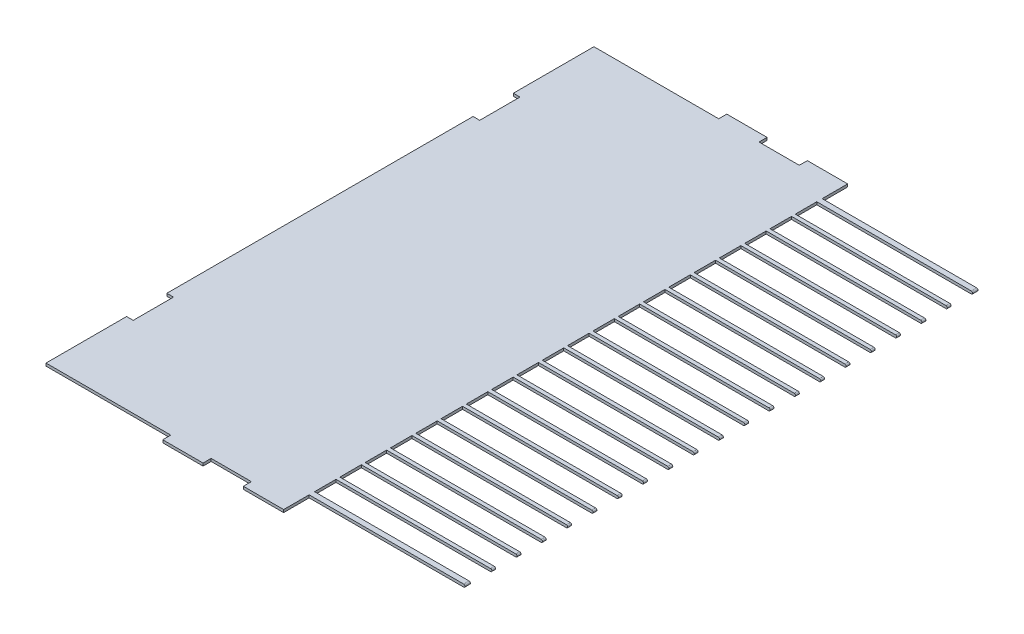
SolidWorks part; units mm, degrees
ref_plane "前视基准面" through (0, 0, 0) normal (0, 0, 1) x (1, 0, 0)
ref_plane "上视基准面" through (0, 0, 0) normal (0, 1, 0) x (1, 0, 0)
ref_plane "右视基准面" through (0, 0, 0) normal (1, 0, 0) x (0, 0, -1)
sketch "草图1" plane through (0, 0, 0) normal (0, 0, 1) x (1, 0, 0)
  line L0 (0, -1.0782) -> (0, -59.0782)
  line L1 (0, -59.0782) -> (150, -59.0782)
  line L3 (24.7207, -21.434) -> (24.7207, -1.0782)
  line L4 (24.7207, -1.0782) -> (0, -1.0782)
  line L5 (150, -59.0782) -> (150, -56.0782)
  line L6 (150, -56.0782) -> (24.7207, -21.434)
  dimension "D1" = 150
  dimension "D2" = 58
  dimension "D3" = 3
extrude "凸台-拉伸1" add sketch "草图1" along normal blind 0.5
sketch "草图2" plane through (0, 0, 0) normal (0, 0, -1) x (-1, 0, 0)
  line L1 (-24.7207, -1.0782) -> (0, -1.0782) construction
  line L2 (-2.47, -1.0782) -> (-2.47, -58.0782)
  line L4 (-149, -59.0782) -> (0, -59.0782)
  line L5 (0, -59.0782) -> (0, -1.0782)
  line L7 (-149, -58.0782) -> (-2.47, -58.0782)
  line L9 (-2.47, -1.0782) -> (0, -1.0782)
  arc A2 (-149, -58.0782) -> (-149, -59.0782) centre (-149, -58.5782) ccw
  point P14 (-150, -58.0782)
  point P17 (-150, -59.0782)
  dimension "D3" = 0.5
  dimension "D1" = 1
  dimension "D2" = 1
  dimension "D4" = 2.47
extrude "凸台-拉伸2" add sketch "草图2" along normal blind 104.5
mirror "镜向3" about plane through (149, -58.5782, -104.5) normal (0, 0, -1) of bodies 102 106
sketch "草图8" plane through (0, -58.0782, 0) normal (0, 1, 0) x (1, 0, 0)
  line L1 (151.4737, 1) -> (91.4737, 1)
  line L2 (151.4737, 1) -> (151.4737, 9)
  line L3 (151.4737, 9) -> (91.4737, 9)
  line L4 (91.4737, 1) -> (91.4737, 9)
  line L5 (151.4737, 1) -> (91.4737, 9) construction
  line L6 (151.4737, 9) -> (91.4737, 1) construction
  line L7 (2.47, 0) -> (149, 0) construction
  line L8 (91.4737, 11) -> (151.4737, 11)
  line L9 (91.4737, 11) -> (91.4737, 19)
  line L10 (91.4737, 19) -> (151.4737, 19)
  line L11 (151.4737, 11) -> (151.4737, 19)
  line L12 (91.4737, 11) -> (151.4737, 19) construction
  line L13 (91.4737, 19) -> (151.4737, 11) construction
  line L14 (91.4737, 20.4211) -> (91.4737, 28.4211)
  line L15 (91.4737, 20.4211) -> (151.4737, 20.4211)
  line L16 (151.4737, 20.4211) -> (151.4737, 28.4211)
  line L17 (91.4737, 28.4211) -> (151.4737, 28.4211)
  line L18 (91.4737, 29.8421) -> (91.4737, 37.8421)
  line L19 (91.4737, 29.8421) -> (151.4737, 29.8421)
  line L20 (151.4737, 29.8421) -> (151.4737, 37.8421)
  line L21 (91.4737, 37.8421) -> (151.4737, 37.8421)
  line L22 (91.4737, 39.2632) -> (91.4737, 47.2632)
  line L23 (91.4737, 39.2632) -> (151.4737, 39.2632)
  line L24 (151.4737, 39.2632) -> (151.4737, 47.2632)
  line L25 (91.4737, 47.2632) -> (151.4737, 47.2632)
  line L26 (91.4737, 48.6842) -> (91.4737, 56.6842)
  line L27 (91.4737, 48.6842) -> (151.4737, 48.6842)
  line L28 (151.4737, 48.6842) -> (151.4737, 56.6842)
  line L29 (91.4737, 56.6842) -> (151.4737, 56.6842)
  line L30 (91.4737, 58.1053) -> (91.4737, 66.1053)
  line L31 (91.4737, 58.1053) -> (151.4737, 58.1053)
  line L32 (151.4737, 58.1053) -> (151.4737, 66.1053)
  line L33 (91.4737, 66.1053) -> (151.4737, 66.1053)
  line L34 (91.4737, 67.5263) -> (91.4737, 75.5263)
  line L35 (91.4737, 67.5263) -> (151.4737, 67.5263)
  line L36 (151.4737, 67.5263) -> (151.4737, 75.5263)
  line L37 (91.4737, 75.5263) -> (151.4737, 75.5263)
  line L38 (91.4737, 76.9474) -> (91.4737, 84.9474)
  line L39 (91.4737, 76.9474) -> (151.4737, 76.9474)
  line L40 (151.4737, 76.9474) -> (151.4737, 84.9474)
  line L41 (91.4737, 84.9474) -> (151.4737, 84.9474)
  line L42 (91.4737, 86.3684) -> (91.4737, 94.3684)
  line L43 (91.4737, 86.3684) -> (151.4737, 86.3684)
  line L44 (151.4737, 86.3684) -> (151.4737, 94.3684)
  line L45 (91.4737, 94.3684) -> (151.4737, 94.3684)
  line L46 (91.4737, 95.7895) -> (91.4737, 103.7895)
  line L47 (91.4737, 95.7895) -> (151.4737, 95.7895)
  line L48 (151.4737, 95.7895) -> (151.4737, 103.7895)
  line L49 (91.4737, 103.7895) -> (151.4737, 103.7895)
  line L50 (91.4737, 105.2105) -> (91.4737, 113.2105)
  line L51 (91.4737, 105.2105) -> (151.4737, 105.2105)
  line L52 (151.4737, 105.2105) -> (151.4737, 113.2105)
  line L53 (91.4737, 113.2105) -> (151.4737, 113.2105)
  line L54 (91.4737, 114.6316) -> (91.4737, 122.6316)
  line L55 (91.4737, 114.6316) -> (151.4737, 114.6316)
  line L56 (151.4737, 114.6316) -> (151.4737, 122.6316)
  line L57 (91.4737, 122.6316) -> (151.4737, 122.6316)
  line L58 (91.4737, 124.0526) -> (91.4737, 132.0526)
  line L59 (91.4737, 124.0526) -> (151.4737, 124.0526)
  line L60 (151.4737, 124.0526) -> (151.4737, 132.0526)
  line L61 (91.4737, 132.0526) -> (151.4737, 132.0526)
  line L62 (91.4737, 133.4737) -> (91.4737, 141.4737)
  line L63 (91.4737, 133.4737) -> (151.4737, 133.4737)
  line L64 (151.4737, 133.4737) -> (151.4737, 141.4737)
  line L65 (91.4737, 141.4737) -> (151.4737, 141.4737)
  line L66 (91.4737, 142.8947) -> (91.4737, 150.8947)
  line L67 (91.4737, 142.8947) -> (151.4737, 142.8947)
  line L68 (151.4737, 142.8947) -> (151.4737, 150.8947)
  line L69 (91.4737, 150.8947) -> (151.4737, 150.8947)
  line L70 (91.4737, 152.3158) -> (91.4737, 160.3158)
  line L71 (91.4737, 152.3158) -> (151.4737, 152.3158)
  line L72 (151.4737, 152.3158) -> (151.4737, 160.3158)
  line L73 (91.4737, 160.3158) -> (151.4737, 160.3158)
  line L74 (91.4737, 161.7368) -> (91.4737, 169.7368)
  line L75 (91.4737, 161.7368) -> (151.4737, 161.7368)
  line L76 (151.4737, 161.7368) -> (151.4737, 169.7368)
  line L77 (91.4737, 169.7368) -> (151.4737, 169.7368)
  line L78 (91.4737, 171.1579) -> (91.4737, 179.1579)
  line L79 (91.4737, 171.1579) -> (151.4737, 171.1579)
  line L80 (151.4737, 171.1579) -> (151.4737, 179.1579)
  line L81 (91.4737, 179.1579) -> (151.4737, 179.1579)
  line L82 (91.4737, 180.5789) -> (91.4737, 188.5789)
  line L83 (91.4737, 180.5789) -> (151.4737, 180.5789)
  line L84 (151.4737, 180.5789) -> (151.4737, 188.5789)
  line L85 (91.4737, 188.5789) -> (151.4737, 188.5789)
  line L86 (91.4737, 190) -> (91.4737, 198)
  line L87 (91.4737, 190) -> (151.4737, 190)
  line L88 (151.4737, 190) -> (151.4737, 198)
  line L89 (91.4737, 198) -> (151.4737, 198)
  line L90 (2.47, 209) -> (149, 209) construction
  line L91 (151.4737, 200) -> (91.4737, 200)
  line L92 (151.4737, 200) -> (151.4737, 208)
  line L93 (151.4737, 208) -> (91.4737, 208)
  line L94 (91.4737, 200) -> (91.4737, 208)
  line L95 (151.4737, 200) -> (91.4737, 208) construction
  line L96 (151.4737, 208) -> (91.4737, 200) construction
  point P4 (121.4737, 5)
  point P11 (121.4737, 15)
  point P94 (121.4737, 204)
  dimension "D1" = 60
  dimension "D2" = 8
  dimension "D3" = 8
  dimension "D4" = 2
  dimension "D5" = 1
  dimension "D7" = 8
  dimension "D8" = 2
  dimension "D9" = 60
  dimension "D10" = 1
  dimension "D6" = 20
extrude "切除-拉伸2" cut sketch "草图8" against normal blind 10
extrude "凸台-拉伸4" add sketch "草图1<3>" against normal blind 2.5
sketch "草图1<3>" plane through (0, 0, 0) normal (0, 0, 1) x (1, 0, 0) same geometry as "草图1"
ref_plane "基准面1" through (0, 0, -104.5) normal (0, 0, 1) x (1, 0, 0)
mirror "镜向4" about plane through (0, 0, -104.5) normal (0, 0, 1) of "凸台-拉伸4"
mirror "镜向5" about plane through (0, 0, -104.5) normal (0, 0, 1) of "凸台-拉伸4"
sketch "草图7" plane through (0, 0, 0.5) normal (0, 0, 1) x (1, 0, 0)
  line L0 (0, -1.0782) -> (0, -59.0782) construction
  line L1 (8, -45.0782) -> (23, -45.0782) construction
  line L2 (0, -59.0782) -> (150, -59.0782) construction
  line L3 (23, -45.0782) -> (25, -45.0782) construction
  circle A0 centre (8, -45.0782) radius 3.5
  circle A1 centre (25, -45.0782) radius 0.5
  circle A2 centre (23, -45.0782) radius 0.5
  dimension "D1" = 8
  dimension "D3" = 17
  dimension "D4" = 2
  dimension "D2" = 14
extrude "切除-拉伸4" cut sketch "草图7" against normal blind 244
sketch "草图10" plane through (150, 0, 0) normal (1, 0, 0) x (0, 0, -1)
  line L1 (-0.5, -59.0782) -> (2.5, -59.0782)
  line L2 (-0.5, -59.0782) -> (-0.5, 35.9259)
  line L3 (-0.5, 35.9259) -> (2.5, 35.9259)
  line L4 (2.5, -59.0782) -> (2.5, 35.9259)
  line L5 (-0.5, -59.0782) -> (2.5, 35.9259) construction
  line L6 (-0.5, 35.9259) -> (2.5, -59.0782) construction
  line L7 (206.5, -59.0782) -> (209.5, -59.0782)
  line L8 (206.5, -59.0782) -> (206.5, 43.8867)
  line L9 (206.5, 43.8867) -> (209.5, 43.8867)
  line L10 (209.5, -59.0782) -> (209.5, 43.8867)
  line L11 (206.5, -59.0782) -> (209.5, 43.8867) construction
  line L12 (206.5, 43.8867) -> (209.5, -59.0782) construction
  point P4 (1, -11.5762)
  point P10 (208, -7.5957)
extrude "切除-拉伸5" cut sketch "草图10" against normal blind 284
sketch "草图11" plane through (2.47, 0, 0) normal (1, 0, 0) x (0, 0, -1)
  line L1 (206.5, -1.0782) -> (2.5, -1.0782)
  line L2 (206.5, -1.0782) -> (206.5, -58.0782)
  line L3 (206.5, -58.0782) -> (2.5, -58.0782)
  line L4 (2.5, -1.0782) -> (2.5, -58.0782)
  line L5 (206.5, -1.0782) -> (2.5, -58.0782) construction
  line L6 (206.5, -58.0782) -> (2.5, -1.0782) construction
  point P4 (104.5, -29.5782)
extrude "切除-拉伸6" cut sketch "草图11" against normal blind 284
sketch "草图13" plane through (0, -58.0782, 0) normal (0, 1, 0) x (1, 0, 0)
  line L0 (0, 2.5) -> (0, 206.5) construction
  line L1 (0, 32.5) -> (2.47, 32.5)
  line L2 (0, 32.5) -> (0, 47.5)
  line L3 (0, 47.5) -> (2.47, 47.5)
  line L4 (2.47, 32.5) -> (2.47, 47.5)
  line L5 (0, 32.5) -> (2.47, 47.5) construction
  line L6 (0, 47.5) -> (2.47, 32.5) construction
  line L8 (91.4737, 2.5) -> (0, 2.5) construction
  line L9 (-55, 104.5) -> (55, 104.5) construction
  line L10 (0, 161.5) -> (2.47, 176.5) construction
  line L11 (0, 176.5) -> (2.47, 161.5) construction
  line L12 (2.47, 176.5) -> (2.47, 161.5)
  line L13 (0, 161.5) -> (2.47, 161.5)
  line L14 (0, 176.5) -> (0, 161.5)
  line L15 (0, 176.5) -> (2.47, 176.5)
  point P4 (1.235, 40)
  point P17 (1.235, 169)
  dimension "D1" = 15
  dimension "D2" = 30
  dimension "D3" = 114
extrude "切除-拉伸7" cut sketch "草图13" against normal blind 284
sketch "草图14" plane through (0, -59.0782, 0) normal (0, -1, 0) x (-1, 0, 0)
  line L0 (-91.4737, 9) -> (-91.4737, 2.5) construction
  line L1 (-91.4737, 2.5) -> (-76.4737, 2.5)
  line L2 (-91.4737, 2.5) -> (-91.4737, -0.5)
  line L3 (-91.4737, -0.5) -> (-76.4737, -0.5)
  line L4 (-76.4737, 2.5) -> (-76.4737, -0.5)
  line L5 (-91.4737, 2.5) -> (-76.4737, -0.5) construction
  line L6 (-91.4737, -0.5) -> (-76.4737, 2.5) construction
  line L7 (-61.4737, -0.5) -> (-46.4737, -0.5)
  line L8 (-61.4737, -0.5) -> (-61.4737, 2.5)
  line L9 (-61.4737, 2.5) -> (-46.4737, 2.5)
  line L10 (-46.4737, -0.5) -> (-46.4737, 2.5)
  line L11 (-61.4737, -0.5) -> (-46.4737, 2.5) construction
  line L12 (-61.4737, 2.5) -> (-46.4737, -0.5) construction
  point P4 (-83.9737, 1)
  point P9 (-53.9737, 1)
  point P12 (-76.4737, 1)
  dimension "D1" = 15
  dimension "D2" = 0
  dimension "D3" = 15
  dimension "D4" = 15
extrude "凸台-拉伸5" add sketch "草图14" against normal blind 1
mirror "镜向6" about plane through (0, 0, -104.5) normal (0, 0, 1) of "凸台-拉伸5"
sketch "草图17" plane through (0, -58.0782, 0) normal (0, 1, 0) x (1, 0, 0)
  line L0 (91.4737, 198) -> (91.4737, 190) construction
  line L1 (87.4737, 202.5) -> (64.4737, 202.5)
  line L2 (87.4737, 202.5) -> (87.4737, 190.5)
  line L3 (87.4737, 190.5) -> (64.4737, 190.5)
  line L4 (64.4737, 202.5) -> (64.4737, 190.5)
  line L5 (87.4737, 202.5) -> (64.4737, 190.5) construction
  line L6 (87.4737, 190.5) -> (64.4737, 202.5) construction
  line L7 (91.4737, 209.5) -> (76.4737, 209.5) construction
  line L8 (-55, 104.5) -> (55, 104.5) construction
  line L9 (87.4737, 18.5) -> (64.4737, 18.5)
  line L10 (64.4737, 6.5) -> (64.4737, 18.5)
  line L11 (87.4737, 6.5) -> (64.4737, 6.5)
  line L12 (87.4737, 6.5) -> (87.4737, 18.5)
  point P4 (75.9737, 196.5)
  dimension "D1" = 23
  dimension "D2" = 12
  dimension "D3" = 4
  dimension "D4" = 7
